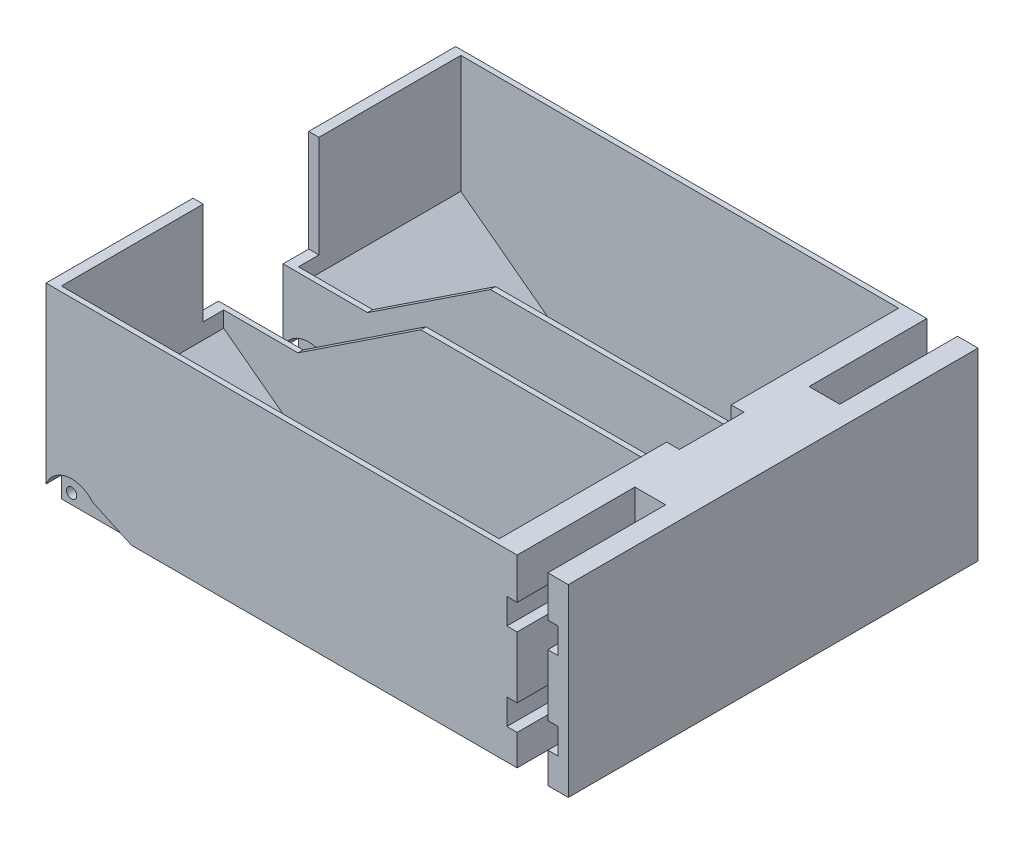
SolidWorks part; units mm, degrees
ref_plane "Front Plane" through (0, 0, 0) normal (0, 0, 1) x (1, 0, 0)
ref_plane "Top Plane" through (0, 0, 0) normal (0, 1, 0) x (1, 0, 0)
ref_plane "Right Plane" through (0, 0, 0) normal (1, 0, 0) x (0, 0, -1)
sketch "Sketch2" plane through (0, 0, 0) normal (0, 1, 0) x (1, 0, 0)
  line L1 (-44.75, -16.85) -> (44.75, -16.85)
  line L2 (-44.75, -16.85) -> (-44.75, 16.85)
  line L3 (-44.75, 16.85) -> (44.75, 16.85)
  line L4 (44.75, -16.85) -> (44.75, 16.85)
  line L5 (-44.75, -16.85) -> (44.75, 16.85) construction
  line L6 (-44.75, 16.85) -> (44.75, -16.85) construction
  point P0 (0, 0)
  dimension "D1" = 89.5
  dimension "D2" = 33.7
extrude "Boss-Extrude1" add sketch "Sketch2" along normal blind 38 contours L2 L3 L4 L1
sketch "Sketch3" plane through (0, 38, 0) normal (0, 1, 0) x (1, 0, 0)
  line L0 (-44.75, 16.85) -> (44.75, 16.85) construction
  line L1 (-42.75, -15.85) -> (42.75, -15.85)
  line L2 (-42.75, -15.85) -> (-42.75, 15.85)
  line L3 (-42.75, 15.85) -> (42.75, 15.85)
  line L4 (42.75, -15.85) -> (42.75, 15.85)
  line L5 (-42.75, -15.85) -> (42.75, 15.85) construction
  line L6 (-42.75, 15.85) -> (42.75, -15.85) construction
  line L7 (44.75, -16.85) -> (44.75, 16.85) construction
  point P0 (0, 0)
  dimension "D1" = 1
  dimension "D2" = 2
extrude "Cut-Extrude1" cut sketch "Sketch3" against normal up to vertex (38 mm away) up to point (-44.75, 0, -16.85)
sketch "Sketch4" plane through (0, 0, -15.85) normal (0, 0, 1) x (1, 0, 0)
  line L0 (-42.75, 0) -> (-42.75, 15)
  line L1 (-42.75, 15) -> (-22.75, 0)
  line L2 (-44.75, 0) -> (44.75, 0) construction
  line L3 (-22.75, 0) -> (-42.75, 0)
  dimension "D1" = 15
  dimension "D2" = 20
extrude "Boss-Extrude2" add sketch "Sketch4" along normal up to vertex (31.7 mm away) up to point (-42.75, 0, 15.85)
sketch "Sketch5" plane through (44.75, 0, 0) normal (1, 0, 0) x (0, 0, -1)
  line L1 (-16.85, 38) -> (16.85, 38)
  line L2 (-16.85, 38) -> (-16.85, 0)
  line L3 (-16.85, 0) -> (16.85, 0)
  line L4 (16.85, 38) -> (16.85, 0)
extrude "Boss-Extrude3" add sketch "Sketch5" along normal blind 2.5
sketch "Sketch6" plane through (0, 0, -16.85) normal (0, 0, -1) x (-1, 0, 0)
  line L0 (44.75, 0) -> (-47.25, 0) construction
  line L1 (-47.25, 38) -> (-45.25, 38)
  line L2 (-47.25, 38) -> (-47.25, 0)
  line L3 (-47.25, 0) -> (-45.25, 0)
  line L4 (-45.25, 38) -> (-45.25, 0)
  dimension "D1" = 2
extrude "Boss-Extrude4" add sketch "Sketch6" along normal blind 6.3 contours L4 L3 L2 L1
ref_plane "Plane1" through (0, 0, -23.15) normal (0, 0, -1) x (-1, 0, 0)
mirror "Mirror1" about plane through (0, 0, -23.15) normal (0, 0, -1) of bodies 105
sketch "Sketch7" plane through (47.25, 0, 0) normal (1, 0, 0) x (0, 0, -1)
  line L0 (23.15, 38) -> (23.15, 0) construction
  line L1 (63.15, 38) -> (-16.85, 38) construction
  line L2 (-16.85, 0) -> (63.15, 0) construction
  line L3 (-16.85, 19) -> (63.15, 19) construction
  line L4 (-16.85, 38) -> (-16.85, 0) construction
  line L5 (63.15, 38) -> (63.15, 0) construction
  line L11 (6.15, 0) -> (40.15, 0)
  line L12 (6.15, 0) -> (6.15, 38)
  line L13 (6.15, 38) -> (40.15, 38)
  line L14 (40.15, 0) -> (40.15, 38)
  line L15 (6.15, 0) -> (40.15, 38) construction
  line L16 (6.15, 38) -> (40.15, 0) construction
  point P12 (23.15, 19)
  point P13 (23.15, 19)
  dimension "D1" = 34
extrude "Boss-Extrude5" add sketch "Sketch7" along normal blind 10
sketch "Sketch8" plane through (0, 0, -6.15) normal (0, 0, 1) x (1, 0, 0)
  line L0 (57.25, 0) -> (47.25, 0) construction
  line L1 (57.25, 38) -> (53.25, 38)
  line L2 (57.25, 38) -> (57.25, 0)
  line L3 (57.25, 0) -> (53.25, 0)
  line L4 (53.25, 38) -> (53.25, 0)
  dimension "D1" = 4
extrude "Boss-Extrude6" add sketch "Sketch8" along normal up to vertex (23 mm away) up to point (47.25, 38, 16.85)
sketch "Sketch9" plane through (0, 0, 16.85) normal (0, 0, 1) x (1, 0, 0)
  line L0 (55.25, 38) -> (55.25, 0) construction
  line L1 (57.25, 38) -> (53.25, 38) construction
  line L2 (53.25, 0) -> (57.25, 0) construction
  line L3 (55.25, 19) -> (52.6863, 19) construction
  line L4 (55.25, 30) -> (45.25, 30)
  line L5 (55.25, 30) -> (55.25, 25)
  line L6 (55.25, 25) -> (45.25, 25)
  line L7 (45.25, 30) -> (45.25, 25)
  line L8 (55.25, 13) -> (45.25, 13)
  line L9 (45.25, 8) -> (45.25, 13)
  line L10 (55.25, 8) -> (45.25, 8)
  line L11 (55.25, 8) -> (55.25, 13)
  dimension "D1" = 10
  dimension "D2" = 5
  dimension "D3" = 25
extrude "Cut-Extrude2" cut sketch "Sketch9" against normal up to vertex (32.7 mm away) up to point (42.75, 38, -15.85)
mirror "Mirror2" about plane through (0, 0, -23.15) normal (0, 0, -1) of "Boss-Extrude6", "Cut-Extrude2"
sketch "Sketch11" plane through (57.25, 0, 0) normal (1, 0, 0) x (0, 0, -1)
  line L0 (63.15, 0) -> (63.15, 38) construction
  line L1 (-16.85, 0) -> (63.15, 0)
  line L2 (-16.85, 0) -> (-16.85, 2)
  line L3 (-16.85, 2) -> (63.15, 2)
  line L4 (63.15, 0) -> (63.15, 2)
  dimension "D1" = 2
extrude "Cut-Extrude3" cut sketch "Sketch11" against normal up to vertex (80 mm away) up to point (-22.75, 0, 15.85)
sketch "Sketch12" plane through (0, 0, 16.85) normal (0, 0, 1) x (1, 0, 0)
  line L0 (-44.75, 38) -> (-44.75, 0) construction
  line L1 (-22.75, 2) -> (-34.3648, 2)
  line L2 (-22.75, 2) -> (-22.75, 0)
  line L3 (-22.75, 0) -> (-44.75, 0)
  arc A0 (-34.3648, 2) -> (-44.75, 0) centre (-39.75, 2) ccw
  dimension "D1" = 5
extrude "Cut-Extrude4" cut sketch "Sketch12" against normal blind 3
ref_plane "Plane2" through (0, 0, 0) normal (0, 0, 1) x (1, 0, 0)
mirror "Mirror3" about plane through (0, 0, 0) normal (0, 0, 1) of "Cut-Extrude4"
mirror "Mirror4" about plane through (0, 0, -23.15) normal (0, 0, -1) of "Mirror3", "Cut-Extrude4"
sketch "Sketch13" plane through (0, 0, 13.85) normal (0, 0, 1) x (1, 0, 0)
  line L0 (-44.75, 0) -> (-22.75, 0) construction
  line L1 (-44.75, 0) -> (-44.75, 4) construction
  circle A0 centre (-42.75, 2) radius 1
  dimension "D1" = 2
  dimension "D2" = 2
  dimension "D3" = 2
extrude "Cut-Extrude5" cut sketch "Sketch13" against normal up to vertex (77 mm away) up to point (-44.75, 4, -63.15)
chamfer "Chamfer1" distance 10 angle 45 1 edges at (-34.3648, 2, 15.35)
chamfer "Chamfer2" distance 10 angle 45 1 edges at (-34.3648, 2, -15.35)
chamfer "Chamfer3" distance 10 angle 45 1 edges at (-34.3648, 2, -30.95)
chamfer "Chamfer4" distance 10 angle 45 1 edges at (-34.3648, 2, -61.65)
sketch "Sketch15" plane through (0, 38, 0) normal (0, 1, 0) x (1, 0, 0)
  line L0 (-44.75, 16.85) -> (45.25, 16.85) construction
  line L1 (42.75, 15.85) -> (-4.25, 15.85)
  line L2 (42.75, 15.85) -> (42.75, 16.85)
  line L3 (42.75, 16.85) -> (-4.25, 16.85)
  line L4 (-4.25, 15.85) -> (-4.25, 16.85)
  dimension "D1" = 47
extrude "Cut-Extrude6" cut sketch "Sketch15" against normal blind 4
sketch "Sketch16" plane through (0, 38, 0) normal (0, 1, 0) x (1, 0, 0)
  line L5 (-44.75, -16.85) -> (-44.75, 16.85) construction
  line L6 (-4.25, 16.85) -> (-44.75, 16.85)
  line L7 (-4.25, 16.85) -> (-4.25, 14.85)
  line L8 (-4.25, 14.85) -> (-44.75, 14.85)
  line L9 (-44.75, 16.85) -> (-44.75, 14.85)
  dimension "D1" = 2
extrude "Cut-Extrude7" cut sketch "Sketch16" against normal blind 19.9 contours L7 L8 L9 L6
sketch "Sketch17" plane through (0, 0, -14.85) normal (0, 0, -1) x (-1, 0, 0)
  line L1 (44.75, 38) -> (42.75, 38)
  line L2 (44.75, 38) -> (44.75, 18.1)
  line L3 (44.75, 18.1) -> (42.75, 18.1)
  line L4 (42.75, 38) -> (42.75, 18.1)
extrude "Cut-Extrude8" cut sketch "Sketch17" against normal blind 3 contours L2 L3 L4 L1
sketch "Sketch18" plane through (0, 0, -15.85) normal (0, 0, 1) x (1, 0, 0)
  line L0 (-4.25, 18.1) -> (-4.25, 34)
  line L1 (-4.25, 34) -> (-28.25, 18.1)
  line L2 (-4.25, 18.1) -> (-42.75, 18.1) construction
  line L3 (-28.25, 18.1) -> (-4.25, 18.1)
  dimension "D1" = 24
extrude "Boss-Extrude7" add sketch "Sketch18" against normal up to vertex (1 mm away) up to point (-4.25, 34, -16.85)
mirror "Mirror5" about plane through (0, 0, -23.15) normal (0, 0, -1) of "Cut-Extrude6", "Cut-Extrude7", "Cut-Extrude8", "Boss-Extrude7"
